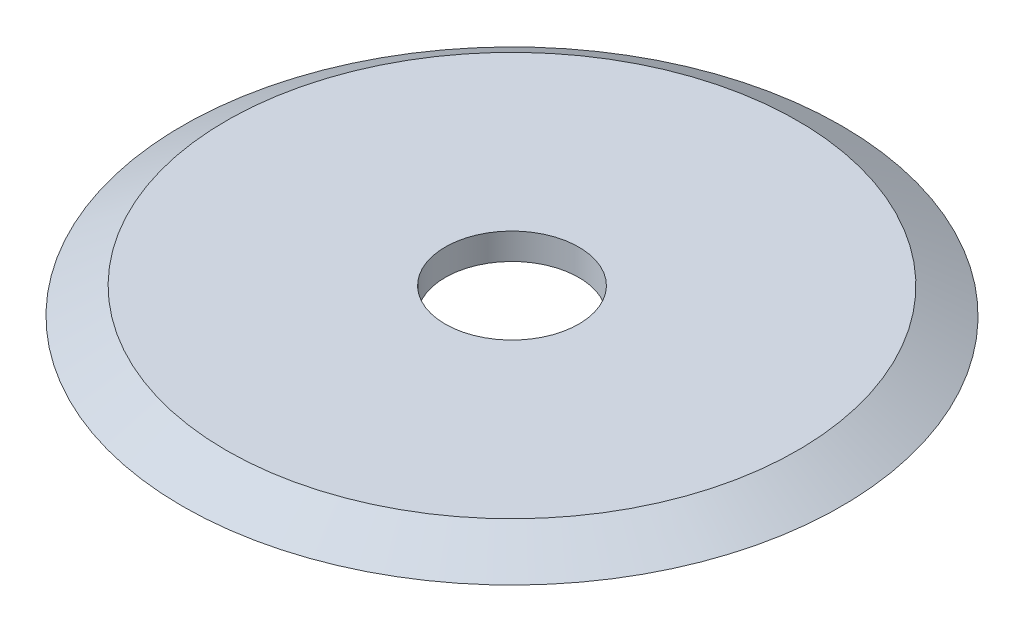
SolidWorks part; units mm, degrees
ref_plane "Спереди" through (0, 0, 0) normal (0, 0, 1) x (1, 0, 0)
ref_plane "Сверху" through (0, 0, 0) normal (0, 1, 0) x (1, 0, 0)
ref_plane "Справа" through (0, 0, 0) normal (1, 0, 0) x (0, 0, -1)
sketch "Эскиз1" plane through (0, 0, 0) normal (0, 1, 0) x (1, 0, 0)
  circle A0 centre (0, 0) radius 37.5
  dimension "D2" = 75
ref_plane "Плоскость1" through (0, 3, 0) normal (0, 1, 0) x (-1, 0, 0)
sketch "Эскиз3" plane through (0, 3, 0) normal (0, 1, 0) x (-1, 0, 0)
  circle A0 centre (0, 0) radius 32.5
  dimension "D1" = 65
loft "По сечениям4" add profiles "Эскиз1", "Эскиз3" connector at (-23.9034, 0, 28.8942) connector at (-21.1381, 3, 24.6867)
sketch "Эскиз5" plane through (0, 3, 0) normal (0, 1, 0) x (1, 0, 0)
  circle A0 centre (0, 0) radius 7.6
  dimension "D1" = 15.2
extrude "Вытянуть3" cut sketch "Эскиз5" against normal through all
